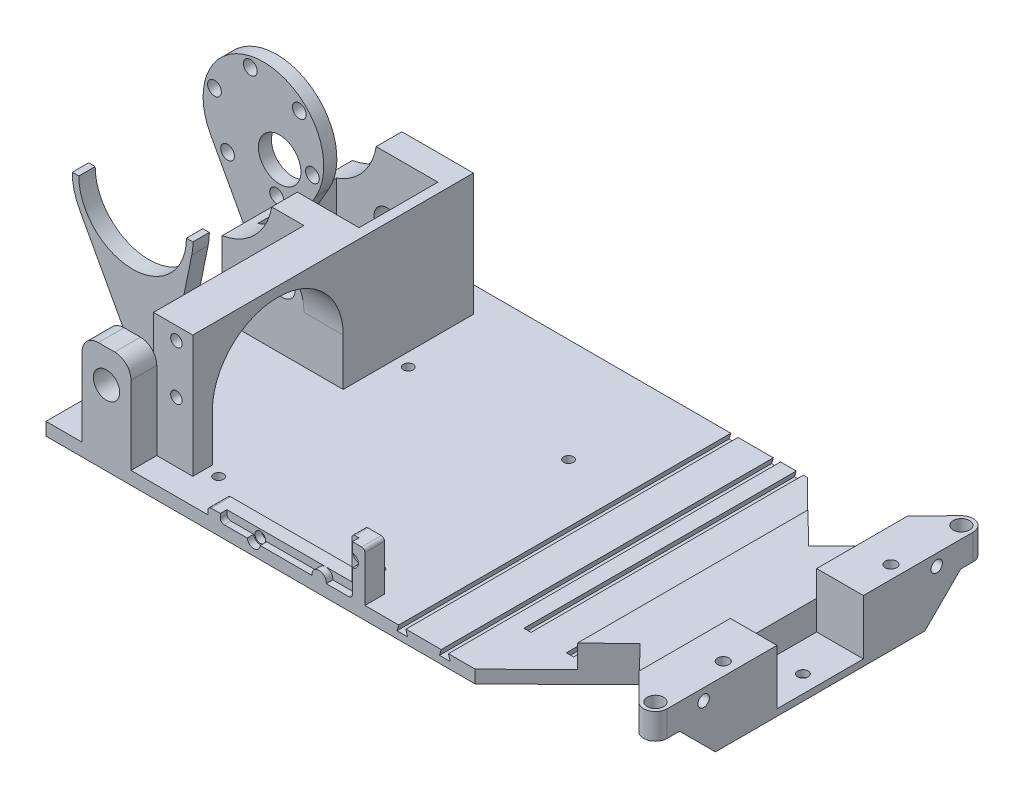
SolidWorks part; units mm, degrees
material "PET"
ref_plane "Alzado" through (0, 0, 0) normal (0, 0, 1) x (1, 0, 0)
ref_plane "Planta" through (0, 0, 0) normal (0, 1, 0) x (1, 0, 0)
ref_plane "Vista lateral" through (0, 0, 0) normal (1, 0, 0) x (0, 0, -1)
sketch "Croquis1" plane through (0, 0, 0) normal (0, 0, 1) x (1, 0, 0)
  circle A0 centre (0, 15) radius 14.5 construction
  circle A1 centre (0, 15) radius 15 construction
  dimension "D2" = 30
  dimension "D3" = 29
  dimension "D1" = 15
sketch "Croquis2" plane through (0, 0, 0) normal (0, 1, 0) x (1, 0, 0)
  line L0 (-14.5, 0) -> (14.5, 0) construction
  line L1 (-15.5, 12.05) -> (15.5, 12.05)
  line L3 (-15.5, -12.05) -> (15.5, -12.05)
  line L4 (15.5, 12.05) -> (15.5, -12.05)
  line L7 (-18.5, 19.9) -> (18.5, 19.9)
  line L9 (-18.5, -19.9) -> (18.5, -19.9)
  line L11 (23.35, 19.9) -> (23.35, -19.9) construction
  line L12 (-23.35, 19.9) -> (-23.35, -19.9) construction
  line L14 (18.5, -19.9) -> (18.5, 19.9)
  line L15 (-15.5, 12.05) -> (-15.5, -12.05)
  line L16 (-23.35, 19.9) -> (23.35, 19.9) construction
  line L17 (-23.35, -19.9) -> (23.35, -19.9) construction
  line L18 (-15.5, 12.05) -> (-15.5, -12.05) construction
  line L19 (-18.5, 19.9) -> (-18.5, -19.9)
  point P0 (0, 0)
  dimension "D1" = 15.5
  dimension "D2" = 24.1
  dimension "D4" = 39.8
  dimension "D5" = 3
  dimension "D6" = 3
  dimension "D7" = 12.05
  dimension "D8" = 15.5
  dimension "D3" = 7.85
extrude "Saliente-Extruir1" add sketch "Croquis2" along normal blind 33.55 and the other way blind 3.9
sketch "Croquis5" plane through (0, 0, 19.9) normal (0, 0, 1) x (1, 0, 0)
  circle A0 centre (0, 15) radius 3.775
  dimension "D1" = 7.55
extrude "Cortar-Extruir4" cut sketch "Croquis5" against normal through all
ref_plane "Plano2" through (0, -7.8, 0) normal (0, 1, 0) x (1, 0, 0)
sketch "Croquis6" plane through (0, -7.8, 0) normal (0, 1, 0) x (1, 0, 0)
  line L1 (-18.5, -73.77) -> (156.91, -73.77)
  line L2 (-18.5, -73.77) -> (-18.5, 27.77)
  line L5 (-18.5, 19.9) -> (-18.5, -19.9) construction
  line L6 (0, 0) -> (15.5, 0) construction
  line L7 (-18.5, 27.77) -> (156.91, 27.77)
  line L8 (-15.5, 12.05) -> (15.5, 12.05)
  line L10 (-15.5, -12.05) -> (15.5, -12.05)
  line L11 (15.5, 12.05) -> (15.5, -12.05)
  line L12 (156.91, 27.77) -> (156.91, -73.77)
  line L13 (-15.5, 12.05) -> (15.5, 12.05) construction
  line L14 (-15.5, 12.05) -> (-15.5, -12.05) construction
  line L15 (-15.5, 12.05) -> (-15.5, -12.05)
  dimension "D1" = 101.54
  dimension "D2" = 73.77
  dimension "D4" = 175.41
extrude "Saliente-Extruir4" add sketch "Croquis6" along normal blind 3.935 contours L1 L2 region at (72.2349, -7.8, 24.007)
sketch "Croquis23" plane through (0, -3.865, 0) normal (0, 1, 0) x (1, 0, 0)
  line L0 (-18.5, -73.77) -> (156.91, -73.77) construction
  line L1 (156.91, 27.77) -> (128.44, 27.77)
  line L2 (156.91, 27.77) -> (156.91, -73.77)
  line L3 (156.91, -73.77) -> (128.44, -73.77)
  line L4 (128.44, 27.77) -> (128.44, -73.77)
  dimension "D1" = 28.47
extrude "Saliente-Extruir16" add sketch "Croquis23" along normal blind 7
sketch "Croquis24" plane through (0, 3.135, 0) normal (0, 1, 0) x (1, 0, 0)
  line L0 (128.44, -58.2804) -> (138.0976, -48.77)
  line L1 (128.44, -73.77) -> (128.44, -58.2804)
  line L2 (163.83, -69.77) -> (163.83, -73.37) construction
  line L3 (167.43, -69.77) -> (167.43, -42.63)
  line L4 (-18.5, -73.77) -> (128.44, -73.77) construction
  line L5 (128.44, -58.2804) -> (112.7106, -73.77)
  line L6 (153.16, -42.63) -> (167.43, -42.63)
  line L10 (156.91, -73.77) -> (128.44, -73.77)
  line L11 (138.0976, -48.77) -> (161.2649, -72.296)
  line L14 (128.44, 27.77) -> (128.44, -73.77) construction
  line L15 (156.91, -48.77) -> (138.0976, -48.77) construction
  line L16 (156.91, -73.77) -> (156.91, -67.8736)
  line L17 (153.16, -42.63) -> (153.16, -64.0656)
  line L18 (156.91, -73.77) -> (156.91, 27.77) construction
  line L19 (-18.5, -73.77) -> (128.44, -73.77) construction
  line L20 (112.7106, -73.77) -> (128.44, -73.77)
  circle A0 centre (163.83, -69.77) radius 2.515
  circle A5 centre (163.83, -69.77) radius 3.6
  line M10 (156.91, -73.77) -> (156.91, 27.77)
  line M12 (128.44, 27.77) -> (128.44, -73.77)
  line M13 (128.44, -73.77) -> (156.91, -73.77)
  line M46 (128.44, 27.77) -> (128.44, -73.77)
  dimension "D1" = 5.03
  dimension "D2" = 4
  dimension "D5" = 25
  dimension "D7" = 7.2
  dimension "D3" = 90
  dimension "D4" = 6.92
  dimension "D6" = 45.44
  dimension "D8" = 31.14
  dimension "D9" = 3.75
extrude "Cortar-Extruir15" cut sketch "Croquis24" against normal through all contours L0 L11 M46 M13 M10 | L5 L20 M12 region at (140.7718, 3.135, 64.418) region at (123.1969, 3.135, 68.6068)
extrude "Saliente-Extruir23" add sketch "Croquis24<4>" along normal blind 7.87 contours A5 L3 | A0 A5 | L17 L11 M10 region at (155.086, 3.135, 54.3257) region at (162.0618, 3.135, 55.2596) region at (162.5037, 3.135, 66.533)
sketch "Croquis24<4>" plane through (0, 3.135, 0) normal (0, 1, 0) x (1, 0, 0) same geometry as "Croquis24"
sketch "Croquis48" plane through (167.43, 0, 0) normal (1, 0, 0) x (0, 0, -1)
  line L0 (-65.97, 3.135) -> (-55.035, -7.8)
  line L1 (-69.77, 3.135) -> (-42.63, 3.135) construction
  line L3 (-55.035, -7.8) -> (-12.1, -7.8)
  line L4 (27.77, -7.8) -> (-67.8736, -7.8) construction
  line L5 (-12.1, -7.8) -> (-12.1, 3.135)
  line L6 (-12.1, 3.135) -> (-65.97, 3.135)
  line L7 (-73.37, 11.005) -> (-73.37, 3.135) construction
  line L8 (27.77, -7.8) -> (-67.8736, -7.8) construction
  dimension "D1" = 7.4
  dimension "D2" = 135
  dimension "D3" = 12.1
extrude "Saliente-Extruir28" add sketch "Croquis48" against normal up to surface (10.52 mm away) up to face at (156.91, -1.239, 24.5674)
sketch "Croquis101" plane through (0, -3.865, 0) normal (0, 1, 0) x (1, 0, 0)
  line L0 (-18.5, -23) -> (167.43, -23) construction
  line L1 (-18.5, -73.77) -> (-18.5, -19.9) construction
  line L2 (167.43, -12.1) -> (167.43, -42.63) construction
  line L3 (-18.5, -73.77) -> (112.7106, -73.77) construction
  line L4 (-18.5, 27.77) -> (128.44, 27.77) construction
  line L5 (0, 27.77) -> (0, -23) construction
  dimension "D1" = 101.54
  dimension "D2" = 50.77
ref_plane "Plano3" through (0, 0, 23) normal (0, 0, 1) x (1, 0, 0)
mirror "Simetría36" about plane through (0, 0, 23) normal (0, 0, 1) of "Saliente-Extruir23", "Saliente-Extruir28", "Cortar-Extruir15"
sketch "Croquis41" plane through (0, 0, 73.77) normal (0, 0, 1) x (1, 0, 0)
  line L0 (-7.5, -3.865) -> (-7.5, 20)
  line L1 (18.5, -3.865) -> (-18.5, -3.865) construction
  line L2 (-2.5, 25) -> (2.5, 25)
  line L3 (7.5, 20) -> (7.5, -3.865)
  line L4 (-18.5, -3.865) -> (112.7106, -3.865) construction
  arc A0 (-7.5, 20) -> (-2.5, 25) centre (-2.5, 20) cw
  arc A1 (2.5, 25) -> (7.5, 20) centre (2.5, 20) cw
  circle A2 centre (0, 15) radius 3.775
  line M8 (112.7106, -3.865) -> (-18.5, -3.865)
  dimension "D1" = 7.55
  dimension "D5" = 5
  dimension "D2" = 7.5
  dimension "D3" = 15
  dimension "D4" = 10
extrude "Saliente-Extruir26" add sketch "Croquis41" against normal blind 7.87 contours A1 L2 A0 L0 L3 A2 M8 region at (0, 9.6633, 73.77)
mirror "Simetría37" about plane through (0, 0, 23) normal (0, 0, 1) of "Saliente-Extruir26"
sketch "Croquis50" plane through (0, 11.005, 0) normal (0, 1, 0) x (1, 0, 0)
  line L3 (153.16, -64.0656) -> (161.2649, -72.296)
  line L4 (167.43, -69.77) -> (167.43, -42.63)
  line L7 (167.43, -69.77) -> (167.43, -42.63)
  line L28 (153.16, -64.0656) -> (161.2649, -72.296)
  line L30 (167.43, -42.63) -> (153.16, -42.63)
  line L33 (167.43, -42.63) -> (153.16, -42.63)
  line L34 (153.16, -42.63) -> (153.16, -64.0656)
  line L35 (153.16, -42.63) -> (153.16, -64.0656)
  circle A0 centre (163.43, -48.63) radius 1.75
  arc A1 (161.2649, -72.296) -> (167.43, -69.77) centre (163.83, -69.77) ccw
  arc A2 (161.2649, -72.296) -> (167.43, -69.77) centre (163.83, -69.77) ccw
  dimension "D2" = 3.5
  dimension "D3" = 21.14
  dimension "D4" = 4
  dimension "D1" = 0
extrude "Cortar-Extruir26" cut sketch "Croquis50" against normal blind 5 contours A0 region at (163.43, 11.005, 48.63)
sketch "Croquis51" plane through (167.43, 0, 0) normal (1, 0, 0) x (0, 0, -1)
  line L1 (-69.77, 11.005) -> (-42.63, 11.005) construction
  line L2 (-69.77, 11.005) -> (-69.77, 3.135) construction
  circle A0 centre (-58.63, 7.505) radius 1.75
  dimension "D1" = 3.5
  dimension "D2" = 11.14
  dimension "D4" = 3.5
extrude "Cortar-Extruir27" cut sketch "Croquis51" against normal blind 5
mirror "Simetría38" about plane through (0, 0, 23) normal (0, 0, 1) of "Cortar-Extruir26", "Cortar-Extruir27"
sketch "Croquis87" plane through (156.91, 0, 0) normal (1, 0, 0) x (0, 0, -1)
  line L4 (-67.8736, -7.8) -> (-55.035, -7.8)
  line L5 (-55.035, -7.8) -> (-65.97, 3.135)
  line L8 (-67.8736, -7.8) -> (-55.035, -7.8)
  line L12 (19.97, 3.135) -> (9.035, -7.8)
  line L36 (-55.035, -7.8) -> (-65.97, 3.135)
  line L39 (-67.8736, 3.135) -> (-67.8736, -7.8)
  line L46 (19.97, 3.135) -> (9.035, -7.8)
  line L54 (-67.8736, 3.135) -> (-67.8736, -7.8)
  line L55 (-65.97, 3.135) -> (-67.8736, 3.135)
  line L63 (9.035, -7.8) -> (21.8736, -7.8)
  line L66 (9.035, -7.8) -> (21.8736, -7.8)
  line L68 (21.8736, -7.8) -> (21.8736, 3.135)
  line L69 (21.8736, -7.8) -> (21.8736, 3.135)
  line L70 (21.8736, 3.135) -> (19.97, 3.135)
  line L71 (21.8736, 3.135) -> (19.97, 3.135)
  line L72 (-65.97, 3.135) -> (-67.8736, 3.135)
  line M9 (-67.8736, -7.8) -> (-55.035, -7.8)
  line M10 (-55.035, -7.8) -> (-65.97, 3.135)
  line M12 (-67.8736, 3.135) -> (-67.8736, -7.8)
  line M59 (-65.97, 3.135) -> (-67.8736, 3.135)
  dimension "D1" = 0
  dimension "D2" = 0
extrude "Cortar-Extruir43" cut sketch "Croquis87" against normal up to next contours M12 M9 M10 M59 | L69 L71 L46 L66 region at (156.91, -3.6843, 63.5121) region at (156.91, -3.6843, -17.5121)
sketch "Croquis91" plane through (0, 0, 73.77) normal (0, 0, 1) x (1, 0, 0)
  circle A0 centre (0, 15) radius 4.025
  dimension "D1" = 8.05
extrude "Cortar-Extruir45" cut sketch "Croquis91" against normal through all from surface starting at face at (-3.775, 15, -12.05)
sketch "Croquis92" plane through (0, 0, -12.05) normal (0, 0, 1) x (1, 0, 0)
  line L0 (-16.617, 31.617) -> (0, 15) construction
  line L1 (-18.5, -7.8) -> (112.7106, -7.8) construction
  line L2 (-16.617, 31.617) -> (-21.5668, 36.5668) construction
  line L3 (-21.5668, 36.5668) -> (-36.5386, 40.5785) construction
  line L4 (-15.5, 33.55) -> (-15.5, -3.865) construction
  line L5 (-18.5, 33.55) -> (18.5, 33.55) construction
  line L6 (-18.5, -3.865) -> (-7.5, -3.865) construction
  line L7 (-18.5, -3.865) -> (-18.5, 33.55) construction
  line L8 (-18.5, -7.8) -> (-37.7863, 27.7731)
  line L9 (-18.5, -7.8) -> (-18.5, 18.3734)
  line L10 (-15.5, 10.135) -> (-5.5794, 27.3577)
  line L11 (-15.5, 10.135) -> (-15.5, 19.1427)
  line L12 (18.5, -3.865) -> (-18.5, -3.865) construction
  circle A0 centre (-16.617, 31.617) radius 2.5
  circle A1 centre (-21.5668, 36.5668) radius 18.45
  circle A2 centre (-16.617, 31.617) radius 3.5
  circle A3 centre (-16.617, 31.617) radius 6.5
  circle A4 centre (-21.5668, 36.5668) radius 15.5 construction
  circle A5 centre (-36.5386, 40.5785) radius 2.1
  circle A6 centre (-25.5785, 51.5386) radius 2.1
  circle A7 centre (-10.6066, 47.5269) radius 2.1
  circle A8 centre (-6.5949, 32.5551) radius 2.1
  circle A9 centre (-17.5551, 21.5949) radius 2.1
  circle A10 centre (-32.5269, 25.6066) radius 2.1
  line M3 (15.5, 33.55) -> (-15.5, 33.55)
  line M4 (-15.5, 33.55) -> (-15.5, -7.8)
  dimension "D1" = 5
  dimension "D5" = 36.9
  dimension "D6" = 1
  dimension "D7" = 13
  dimension "D8" = 31
  dimension "D10" = 4.2
  dimension "D2" = 23.5
  dimension "D3" = 45
  dimension "D4" = 7
  dimension "D9" = 30
  dimension "D12" = 3
  dimension "D13" = 14
  dimension "D11" = 6
extrude "Cortar-Extruir62" cut sketch "Croquis91<2>" against normal up to surface (7.87 mm away) up to face at (3.775, 15, 65.9)
sketch "Croquis91<2>" plane through (0, 0, 73.77) normal (0, 0, 1) x (1, 0, 0) same geometry as "Croquis91"
sketch "Croquis94" plane through (0, -3.865, 0) normal (0, 1, 0) x (1, 0, 0)
  line L0 (18.5, 19.9) -> (18.5, -19.9) construction
  line L3 (7.5, -73.77) -> (112.7106, -73.77) construction
  circle A0 centre (22.5, -4) radius 1.5
  circle A1 centre (22.5, -62) radius 1.5
  circle A2 centre (71.5, -4) radius 1.5
  circle A3 centre (71.5, -62) radius 1.5
  dimension "D1" = 3
  dimension "D5" = 4
  dimension "D2" = 58
  dimension "D3" = 49
  dimension "D4" = 11.77
extrude "Cortar-Extruir46" cut sketch "Croquis94" against normal through all
sketch "Croquis95" plane through (0, 0, 73.77) normal (0, 0, 1) x (1, 0, 0)
  line L0 (122.44, -3.865) -> (124.44, -3.865)
  line L1 (7.5, -3.865) -> (112.7106, -3.865) construction
  line L2 (124.44, -3.865) -> (124.94, -5.565)
  line L3 (124.94, -5.565) -> (121.94, -5.565)
  line L4 (121.94, -5.565) -> (122.44, -3.865)
  line L5 (109.44, -3.865) -> (111.44, -3.865)
  line L6 (111.44, -3.865) -> (111.94, -5.565)
  line L7 (111.94, -5.565) -> (108.94, -5.565)
  line L8 (108.94, -5.565) -> (109.44, -3.865)
  line L9 (102.44, -3.865) -> (104.44, -3.865)
  line L10 (104.44, -3.865) -> (104.94, -5.565)
  line L11 (104.94, -5.565) -> (101.94, -5.565)
  line L12 (101.94, -5.565) -> (102.44, -3.865)
  line L13 (89.44, -3.865) -> (91.44, -3.865)
  line L14 (91.44, -3.865) -> (91.94, -5.565)
  line L15 (91.94, -5.565) -> (88.94, -5.565)
  line L16 (88.94, -5.565) -> (89.44, -3.865)
  line L17 (92.0603, -5.655) -> (88.8197, -5.655)
  line L18 (88.8197, -5.655) -> (89.3727, -3.775)
  line L19 (89.3727, -3.775) -> (91.5073, -3.775)
  line L20 (91.5073, -3.775) -> (92.0603, -5.655)
  line L21 (105.0603, -5.655) -> (101.8197, -5.655)
  line L22 (101.8197, -5.655) -> (102.3727, -3.775)
  line L23 (102.3727, -3.775) -> (104.5073, -3.775)
  line L24 (104.5073, -3.775) -> (105.0603, -5.655)
  line L25 (112.0603, -5.655) -> (108.8197, -5.655)
  line L26 (108.8197, -5.655) -> (109.3727, -3.775)
  line L27 (109.3727, -3.775) -> (111.5073, -3.775)
  line L28 (111.5073, -3.775) -> (112.0603, -5.655)
  line L29 (125.0603, -5.655) -> (121.8197, -5.655)
  line L30 (121.8197, -5.655) -> (122.3727, -3.775)
  line L31 (122.3727, -3.775) -> (124.5073, -3.775)
  line L32 (124.5073, -3.775) -> (125.0603, -5.655)
  line L33 (128.44, 3.135) -> (128.44, -3.865) construction
  point P4 (123.44, -5.565)
  point P18 (103.44, -5.565)
  point P21 (110.44, -5.565)
  point P22 (90.44, -5.565)
  dimension "D1" = 1.7
  dimension "D2" = 0.5
  dimension "D3" = 0.5
  dimension "D4" = 5
  dimension "D5" = 3
  dimension "D6" = 0.5
  dimension "D7" = 0.5
  dimension "D8" = 0.5
  dimension "D9" = 7
  dimension "D10" = 13
  dimension "D11" = 13
  dimension "D12" = 0.09
extrude "Cortar-Extruir47" cut sketch "Croquis95" along normal offset from surface (83.27 mm away) 18.27 from surface contours L25 L26 L27 L28 | L29 L30 L31 L32 up to face at (4.025, 15, 73.77) starting at face at (-4.025, 15, -27.77)
extrude "Cortar-Extruir61" cut sketch "Croquis95<3>" against normal through all contours L24 L21 L22 L23 | L20 L17 L18 L19
sketch "Croquis95<3>" plane through (0, 0, 73.77) normal (0, 0, 1) x (1, 0, 0) same geometry as "Croquis95"
sketch "Croquis96" plane through (0, -3.865, 0) normal (0, 1, 0) x (1, 0, 0)
  line L0 (0, -23) -> (163.83, 23.77)
  line L1 (7.5, 27.77) -> (89.3462, 27.77) construction
  dimension "D1" = 164.067
extrude "Cortar-Extruir48" cut sketch "Croquis92" against normal through all from surface contours A1 starting at face at (0, 14.8425, 19.9)
extrude "Saliente-Extruir32" add sketch "Croquis92<6>" against normal blind 4 from offset 16.27 contours A8 A1 A3 A10 A9 A7 A6 A5 M3 M4 | A8 A3 A1 M3 M4 | A1 L10 M4 | A1 L8 L9 region at (-23.9801, 10.5374, -12.05) region at (-23.4863, 38.378, -12.05) region at (-12.7576, 17.7169, -12.05) region at (-10.0814, 26.2362, -12.05)
sketch "Croquis92<6>" plane through (0, 0, -12.05) normal (0, 0, 1) x (1, 0, 0) same geometry as "Croquis92"
sketch "Croquis111" plane through (0, 0, 3.37) normal (0, 0, 1) x (1, 0, 0)
  line L4 (153.16, 3.135) -> (167.43, 3.135)
  line L5 (167.43, 3.135) -> (167.43, 11.005)
  line L6 (167.43, 11.005) -> (153.16, 11.005)
  line L7 (153.16, 11.005) -> (153.16, 3.135)
  line L8 (153.16, 3.135) -> (167.43, 3.135)
  line L9 (167.43, 3.135) -> (167.43, 11.005)
  line L10 (167.43, 11.005) -> (153.16, 11.005)
  line L11 (153.16, 11.005) -> (153.16, 3.135)
  dimension "D1" = 0
extrude "Saliente-Extruir36" add sketch "Croquis111" along normal up to surface (39.26 mm away) up to face at (160.295, 7.07, 42.63)
sketch "Croquis99" plane through (0, 11.005, 0) normal (0, 1, 0) x (1, 0, 0)
  line L0 (167.43, -69.77) -> (167.43, 23.77) construction
  line L1 (167.43, -36) -> (153.36, -36)
  line L2 (167.43, -36) -> (167.43, -10)
  line L3 (167.43, -10) -> (153.36, -10)
  line L4 (153.36, -36) -> (153.36, -10)
  line L5 (167.63, -9.8) -> (153.16, -9.8)
  line L6 (153.16, -36.2) -> (153.16, -9.8)
  line L7 (167.63, -36.2) -> (153.16, -36.2)
  line L8 (167.63, -36.2) -> (167.63, -9.8)
  line L9 (7.5, -73.77) -> (89.3462, -73.77) construction
  line L10 (7.5, 27.77) -> (89.3462, 27.77) construction
  point P15 (167.43, -23)
  dimension "D1" = 14.07
  dimension "D2" = 26
  dimension "D4" = 101.54
  dimension "D5" = 50.77
extrude "Cortar-Extruir50" cut sketch "Croquis99" against normal offset from surface (16.805 mm away) 2 contours L7 L6 L5 L8 up to face at (22.5, -7.8, 63.5)
sketch "Croquis100" plane through (0, -5.8, 0) normal (0, 1, 0) x (1, 0, 0)
  line L0 (167.43, -36.2) -> (167.43, -9.8) construction
  line L1 (-18.5, -23) -> (167.43, -23) construction
  circle A2 centre (162.17, -23) radius 1.6
  dimension "D2" = 5.26
  dimension "D3" = 3.2
extrude "Cortar-Extruir51" cut sketch "Croquis100" against normal through all contours A2
sketch "Croquis102" plane through (0, 0, 4.22) normal (0, 0, 1) x (1, 0, 0)
  line L0 (-21.3288, 55.0152) -> (-21.3288, -2.5824) construction
  line L1 (-18.5, -7.8) -> (-37.7863, 27.7731) construction
  arc A0 (-5.5794, 27.3577) -> (-37.7863, 27.7731) centre (-21.5668, 36.5668) ccw construction
extrude "Saliente-Extruir34" add sketch "Croquis92<7>" along normal blind 5 from offset 51.27 contours A1 L8 L9 | A1 region at (-23.9801, 10.5374, -12.05)
sketch "Croquis92<7>" plane through (0, 0, -12.05) normal (0, 0, 1) x (1, 0, 0) same geometry as "Croquis92"
sketch "Croquis109" plane through (0, 0, 44.22) normal (0, 0, 1) x (1, 0, 0)
  line L0 (-40.0168, 36.5668) -> (-3.1168, 36.5668)
  line L1 (-18.5, 18.3734) -> (-18.5, -3.865)
  line L2 (-18.5, -3.865) -> (-11, -3.865)
  line L3 (-18.5, -3.865) -> (167.43, -3.865) construction
  line L4 (-11, -3.865) -> (-3.4905, 32.8718)
  arc A0 (-18.5, 18.3734) -> (-37.7863, 27.7731) centre (-21.5668, 36.5668) ccw construction
  circle A1 centre (-21.5668, 36.5668) radius 16.45
  arc A2 (-18.5, 18.3734) -> (-3.4905, 32.8718) centre (-21.5668, 36.5668) ccw
  circle A3 centre (-21.5668, 36.5668) radius 18.45
  line M5 (-18.5, -3.865) -> (-18.5, 18.3734)
  arc M6 (-18.5, 18.3734) -> (-37.7863, 27.7731) centre (-21.5668, 36.5668) ccw
  dimension "D1" = 32.9
  dimension "D2" = 7.5
extrude "Saliente-Extruir35" add sketch "Croquis109" against normal blind 5 contours L2 L4 M6 M5 region at (-12.7697, 10.2727, 44.22)
extrude "Cortar-Extruir55" cut sketch "Croquis109<3>" against normal blind 5 contours A1 L0 M6 | A1 region at (-21.5668, 53.4293, 44.22)
sketch "Croquis109<3>" plane through (0, 0, 44.22) normal (0, 0, 1) x (1, 0, 0) same geometry as "Croquis109"
sketch "Croquis114" plane through (0, 0, 73.77) normal (0, 0, 1) x (1, 0, 0)
  line L0 (36, -3.8) -> (43.2, -3.8)
  line L1 (35, -2.8) -> (35, 3.8)
  line L2 (36, 16.2) -> (43.2, 16.2)
  line L3 (75, -2.8) -> (75, 4.4)
  line L4 (35, -3.8) -> (75, 16.2) construction
  line L5 (35, 16.2) -> (75, -3.8) construction
  line L6 (-18.5, -7.8) -> (112.7106, -7.8) construction
  line L7 (35, 8.6) -> (35, 15.2)
  line L8 (67.4, -3.8) -> (74, -3.8)
  line L9 (67.4, 16.2) -> (74, 16.2)
  line L10 (46.8, 16.2) -> (62.6, 16.2)
  line L11 (43.4, 16.2) -> (46.6, 16.2)
  line L12 (46.8, -3.8) -> (62.6, -3.8)
  line L13 (43.4, -3.8) -> (46.6, -3.8)
  line L14 (75, 4.6) -> (75, 7.8)
  line L15 (75, 8) -> (75, 15.2)
  line L16 (46.99, 16.4) -> (62.8091, 16.4)
  line L18 (67.1909, 16.4) -> (74, 16.4)
  line L19 (75.2, 8.19) -> (75.2, 15.2)
  line L20 (75.2, -2.8) -> (75.2, 4.21)
  line L21 (67.1909, -4) -> (74, -4)
  line L22 (46.99, -4) -> (62.8091, -4)
  line L23 (36, -4) -> (43.01, -4)
  line L24 (34.8, -2.8) -> (34.8, 4.0091)
  line L25 (34.8, 8.3909) -> (34.8, 15.2)
  line L26 (36, 16.4) -> (43.01, 16.4)
  line L27 (79, -3.865) -> (79, 10.135)
  line L28 (-18.5, -3.865) -> (167.43, -3.865) construction
  line L29 (78, 11.135) -> (74, 11.135)
  line L30 (73, 10.135) -> (73, -1.6)
  line L31 (73, -1.6) -> (32, -1.6)
  line L32 (31, -2.6) -> (31, -3.865)
  line L33 (31, -3.865) -> (79, -3.865)
  arc A0 (46.8, 16.2) -> (43.2, 16.2) centre (45, 16.2) ccw
  arc A1 (43.2, -3.8) -> (46.8, -3.8) centre (45, -3.8) ccw
  arc A2 (35, 3.8) -> (35, 8.6) centre (35, 6.2) ccw
  arc A3 (62.6, 16.2) -> (67.4, 16.2) centre (65, 16.2) ccw
  circle A4 centre (45, 16.2) radius 1.6
  arc A5 (74, 16.2) -> (75, 15.2) centre (74, 15.2) cw
  circle A6 centre (45, -3.8) radius 1.6
  arc A7 (36, -3.8) -> (35, -2.8) centre (36, -2.8) cw
  arc A8 (74, -3.8) -> (75, -2.8) centre (74, -2.8) ccw
  arc A9 (35, 15.2) -> (36, 16.2) centre (36, 15.2) cw
  arc A10 (67.4, -3.8) -> (62.6, -3.8) centre (65, -3.8) ccw
  arc A11 (75, 4.4) -> (75, 8) centre (75, 6.2) ccw
  circle A12 centre (75, 6.2) radius 1.6
  arc A13 (62.8091, 16.4) -> (67.1909, 16.4) centre (65, 16.2) ccw
  arc A14 (74, 16.4) -> (75.2, 15.2) centre (74, 15.2) cw
  arc A15 (75.2, 4.21) -> (75.2, 8.19) centre (75, 6.2) ccw
  arc A16 (74, -4) -> (75.2, -2.8) centre (74, -2.8) ccw
  arc A17 (67.1909, -4) -> (62.8091, -4) centre (65, -3.8) ccw
  arc A18 (43.01, -4) -> (46.99, -4) centre (45, -3.8) ccw
  arc A19 (36, -4) -> (34.8, -2.8) centre (36, -2.8) cw
  arc A20 (34.8, 4.0091) -> (34.8, 8.3909) centre (35, 6.2) ccw
  arc A21 (34.8, 15.2) -> (36, 16.4) centre (36, 15.2) cw
  arc A22 (46.99, 16.4) -> (43.01, 16.4) centre (45, 16.2) ccw
  arc A23 (32, -1.6) -> (31, -2.6) centre (32, -2.6) ccw
  arc A24 (74, 11.135) -> (73, 10.135) centre (74, 10.135) ccw
  arc A25 (79, 10.135) -> (78, 11.135) centre (78, 10.135) ccw
  point P0 (55, 6.2)
  line M28 (89.3462, -3.865) -> (7.5, -3.865)
  dimension "D2" = 1
  dimension "D3" = 4.8
  dimension "D4" = 3.2
  dimension "D5" = 3.6
  dimension "D16" = 1
  dimension "D1" = 40
  dimension "D6" = 20
  dimension "D7" = 10
  dimension "D8" = 30
  dimension "D9" = 4
  dimension "D10" = 55
  dimension "D12" = 4
  dimension "D13" = 4
  dimension "D14" = 15
  dimension "D15" = 2
  dimension "D11" = 0.2
extrude "Saliente-Extruir38" add sketch "Croquis114" against normal blind 6 contours L33 L27 A25 L29 A24 L30 L31 A23 L32
extrude "Cortar-Extruir56" cut sketch "Croquis114<3>" against normal blind 2 contours L23 A18 L22 A17 L21 A16 L20 A15 L19 A14 L18 A13 L16 A22 L26 A21 L25 A20 L24 A19
sketch "Croquis114<3>" plane through (0, 0, 73.77) normal (0, 0, 1) x (1, 0, 0) same geometry as "Croquis114"
extrude "Cortar-Extruir57" cut sketch "Croquis114<4>" against normal blind 4 contours A6 M28 | L13 A6 | L14 A12 | L14 A12 | L13 A6 M28 region at (45, -3.8325, 73.77) region at (45, -4.5143, 73.77) region at (45, -3.1209, 73.77) region at (74.3209, 6.2, 73.77) region at (75.6791, 6.2, 73.77)
sketch "Croquis114<4>" plane through (0, 0, 73.77) normal (0, 0, 1) x (1, 0, 0) same geometry as "Croquis114"
sketch "Croquis118" plane through (0, -3.865, 0) normal (0, 1, 0) x (1, 0, 0)
  line L0 (7.5, -73.77) -> (31, -73.77) construction
  line L1 (6.5, -59.9) -> (18.5, -59.9)
  line L2 (6.5, -59.9) -> (6.5, -65.9)
  line L3 (6.5, -65.9) -> (18.5, -65.9)
  line L4 (18.5, -59.9) -> (18.5, -65.9)
  line L5 (6.5, -59.9) -> (18.5, -65.9) construction
  line L6 (6.5, -65.9) -> (18.5, -59.9) construction
  line L7 (18.5, 19.9) -> (18.5, -19.9) construction
  line L9 (7.5, -65.9) -> (7.5, -73.77) construction
  point P0 (12.5, -62.9)
  dimension "D1" = 7.87
  dimension "D2" = 6
  dimension "D3" = 1
extrude "Saliente-Extruir41" add sketch "Croquis118" along normal up to surface (37.415 mm away) up to face at (6.8175, 33.55, 0)
sketch "Croquis119" plane through (0, 0, 65.9) normal (0, 0, 1) x (1, 0, 0)
  line L0 (18.5, 33.55) -> (18.5, -3.865) construction
  line L1 (6.5, 33.55) -> (18.5, 33.55) construction
  circle A0 centre (13.5, 29.55) radius 1.75
  circle A1 centre (13.5, 14.55) radius 1.75
  dimension "D1" = 5
  dimension "D2" = 4
  dimension "D3" = 15
  dimension "D4" = 3.5
extrude "Cortar-Extruir60" cut sketch "Croquis119" against normal blind 6
mirror "Simetría39" about plane through (0, 0, 23) normal (0, 0, 1) of "Cortar-Extruir60"
sketch "Croquis120" plane through (0, 0, 59.9) normal (0, 0, -1) x (-1, 0, 0)
  line L0 (-6.5, 33.55) -> (-6.5, -3.865) construction
  line L1 (-18.5, 33.55) -> (-6.5, 33.55)
  line L2 (-18.5, 33.55) -> (-18.5, 30.55)
  line L3 (-18.5, 30.55) -> (-6.5, 30.55)
  line L4 (-6.5, 33.55) -> (-6.5, 30.55)
  point P5 (-7.6677, 30.55)
  dimension "D1" = 3
extrude "Saliente-Extruir42" add sketch "Croquis120" along normal up to surface (40 mm away) up to face at (-0.1871, 15.0641, 19.9)
fillet "Redondeo1" radius 20 2 edges at (9.2819, 30.55, 59.9) (12.5, 30.55, 19.9)
sketch "Croquis122" plane through (0, 0, -27.77) normal (0, 0, -1) x (-1, 0, 0)
  line L0 (18.5, -7.8) -> (-112.7106, -7.8) construction
  line L1 (-31, -3.865) -> (-79, -3.865) construction
  line L2 (-18.5, -3.865) -> (-18.5, 33.55) construction
  circle A0 centre (-66.12, -5.8325) radius 0.4
  circle A1 centre (-63.58, -5.8325) radius 0.4
  circle A2 centre (-61.04, -5.8325) radius 0.4
  circle A3 centre (-58.5, -5.8325) radius 0.4
  point P8 (0, 0)
  point P9 (0, 0)
  point P10 (0, 0)
  point P11 (0, 0)
  dimension "D1" = 0.8
  dimension "D2" = 3.935
  dimension "D3" = 1.9675
  dimension "D4" = 2.54
  dimension "D5" = 2.54
  dimension "D6" = 2.54
  dimension "D7" = 40
extrude "Cortar-Extruir63" cut sketch "Croquis122" against normal blind 10
equation "\"pin hole\"=4.97"
equation "\"pin hole 2\"=6.2"
equation "\"centros 8\"= 8"
equation "\"altura\"=7.87"
equation "\"D1@Saliente-Extruir1\"=\"altura\"+35"
equation "\"desaface\"=0.85"
equation "\"D2@Croquis6\"=\"D1@Croquis6\"/2+23"
equation "\"D1@Saliente-Extruir4\"= \"altura\" / 2"
equation "\"injertos\"= 3.5"
equation "\"D1\"= \"altura\" / 2"
equation "\"D1@Saliente-Extruir23\"=\"altura\""
equation "\"D1@Saliente-Extruir26\"=\"altura\""
equation "\"insetar pz lego\"= 7.55"
equation "\"rotacion eje\"=5.05"
equation "\"D1@Croquis5\"=\"insetar pz lego\""
equation "\"D2\"= \"rotacion eje\""
equation "\"D1@Croquis41\"=\"insetar pz lego\""
equation "\"D2@Croquis101\"=\"D1@Croquis101\"/2"
equation "\"D5@Croquis99\"=\"D4@Croquis99\"/2"
equation "\"D3@Croquis122\"=\"D2@Croquis122\"/2"
